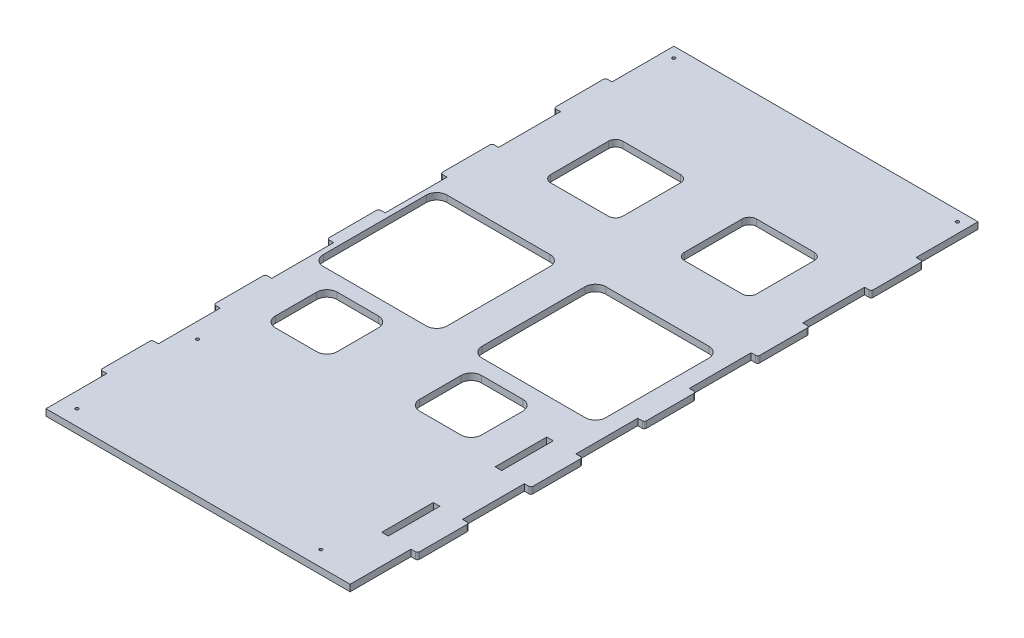
SolidWorks part; units mm, degrees
material "Beech"
ref_plane "Front Plane" through (0, 0, 0) normal (0, 0, 1) x (1, 0, 0)
ref_plane "Top Plane" through (0, 0, 0) normal (0, 1, 0) x (1, 0, 0)
ref_plane "Right Plane" through (0, 0, 0) normal (1, 0, 0) x (0, 0, -1)
sketch "Sketch1" plane through (0, 0, 0) normal (0, 1, 0) x (1, 0, 0)
  line L1 (0, 0) -> (295, 0)
  line L2 (0, 0) -> (0, 59)
  line L3 (0, 609) -> (295, 609)
  line L4 (295, 0) -> (295, 59)
  line L5 (0, 59) -> (-6.35, 59)
  line L7 (0, 109) -> (-6.35, 109)
  line L8 (-6.35, 59) -> (-6.35, 109)
  line L9 (0, 169) -> (-6.35, 169)
  line L10 (-6.35, 169) -> (-6.35, 219)
  line L11 (0, 219) -> (-6.35, 219)
  line L13 (0, 279) -> (-6.35, 279)
  line L14 (-6.35, 279) -> (-6.35, 329)
  line L15 (0, 329) -> (-6.35, 329)
  line L17 (0, 389) -> (-6.35, 389)
  line L18 (-6.35, 389) -> (-6.35, 439)
  line L19 (0, 439) -> (-6.35, 439)
  line L21 (0, 499) -> (-6.35, 499)
  line L22 (-6.35, 499) -> (-6.35, 549)
  line L23 (0, 549) -> (-6.35, 549)
  line L25 (295, 59) -> (301.35, 59)
  line L27 (295, 109) -> (301.35, 109)
  line L28 (301.35, 59) -> (301.35, 109)
  line L29 (295, 169) -> (301.35, 169)
  line L30 (301.35, 169) -> (301.35, 219)
  line L31 (295, 219) -> (301.35, 219)
  line L33 (295, 279) -> (301.35, 279)
  line L34 (301.35, 279) -> (301.35, 329)
  line L35 (295, 329) -> (301.35, 329)
  line L37 (295, 389) -> (301.35, 389)
  line L38 (301.35, 389) -> (301.35, 439)
  line L39 (295, 439) -> (301.35, 439)
  line L41 (295, 499) -> (301.35, 499)
  line L42 (301.35, 499) -> (301.35, 549)
  line L43 (295, 549) -> (301.35, 549)
  line L44 (0, 549) -> (0, 609)
  line L46 (0, 329) -> (0, 389)
  line L49 (0, 219) -> (0, 279)
  line L50 (0, 109) -> (0, 169)
  line L51 (295, 109) -> (295, 169)
  line L52 (295, 219) -> (295, 279)
  line L53 (295, 329) -> (295, 389)
  line L54 (295, 439) -> (295, 499)
  line L55 (295, 549) -> (295, 609)
  line L56 (0, 439) -> (0, 499)
  dimension "D1" = 609
  dimension "D2" = 295
  dimension "D3" = 6.35
  dimension "D4" = 50
  dimension "D5" = 59
  dimension "D7" = 60
  dimension "D8" = 50
  dimension "D9" = 6.35
  dimension "D11" = 59
  dimension "D12" = 60
  dimension "D6" = 5
  dimension "D10" = 5
extrude "Boss-Extrude1" add sketch "Sketch1" along normal blind 6.35
fillet "Fillet1" radius 2 20 edges at (301.35, 3.175, -549) (301.35, 3.175, -499) (301.35, 3.175, -439) (301.35, 3.175, -389) (301.35, 3.175, -329) (301.35, 3.175, -279) (301.35, 3.175, -219) (301.35, 3.175, -169) (301.35, 3.175, -109) (301.35, 3.175, -59) (-6.35, 3.175, -59) (-6.35, 3.175, -109) (-6.35, 3.175, -169) (-6.35, 3.175, -219) (-6.35, 3.175, -279) (-6.35, 3.175, -329) (-6.35, 3.175, -389) (-6.35, 3.175, -439) (-6.35, 3.175, -499) (-6.35, 3.175, -549)
sketch "Sketch2" plane through (0, 6.35, 0) normal (0, 1, 0) x (1, 0, 0)
  line L0 (266.65, 0) -> (266.65, 100) construction
  line L1 (0, 0) -> (295, 0) construction
  line L2 (0, 609) -> (0, 0) construction
  line L3 (295, 609) -> (295, 0) construction
  line L4 (0, 150) -> (266.65, 100) construction
  line L5 (266.65, 169) -> (266.65, 219)
  line L6 (266.65, 59) -> (273, 59)
  line L7 (266.65, 59) -> (266.65, 109)
  line L8 (266.65, 109) -> (273, 109)
  line L9 (273, 59) -> (273, 109)
  line L10 (266.65, 169) -> (273, 169)
  line L11 (273, 169) -> (273, 219)
  line L12 (266.65, 219) -> (273, 219)
  line L13 (0, 84.2124) -> (266.65, 84) construction
  line L14 (55.0424, 504.4355) -> (111.0424, 504.4355)
  line L15 (48.0424, 497.4355) -> (48.0424, 441.4355)
  line L16 (55.0424, 434.4355) -> (111.0424, 434.4355)
  line L17 (118.0424, 497.4355) -> (118.0424, 441.4355)
  line L18 (185.2335, 503.9695) -> (241.2335, 503.9695)
  line L19 (178.2335, 496.9695) -> (178.2335, 440.9695)
  line L20 (185.2335, 433.9695) -> (241.2335, 433.9695)
  line L21 (248.2335, 496.9695) -> (248.2335, 440.9695)
  line L22 (43.325, 239.1432) -> (83.325, 239.1432)
  line L23 (33.325, 229.1432) -> (33.325, 189.1432)
  line L24 (43.325, 179.1432) -> (83.325, 179.1432)
  line L25 (93.325, 229.1432) -> (93.325, 189.1432)
  line L26 (33.325, 239.1432) -> (93.325, 179.1432) construction
  line L27 (33.325, 179.1432) -> (93.325, 239.1432) construction
  line L32 (133.325, 0) -> (133.325, 609) construction
  line L33 (295, 609) -> (0, 609) construction
  line L34 (5, 373.9596) -> (125, 373.9596)
  line L35 (5, 373.9596) -> (5, 253.9596)
  line L36 (5, 253.9596) -> (125, 253.9596)
  line L37 (125, 373.9596) -> (125, 253.9596)
  line L38 (159, 373.9596) -> (279, 373.9596)
  line L39 (159, 373.9596) -> (159, 253.9596)
  line L40 (159, 253.9596) -> (279, 253.9596)
  line L41 (279, 373.9596) -> (279, 253.9596)
  line L42 (233.325, 179.1432) -> (173.325, 239.1432) construction
  line L43 (233.325, 239.1432) -> (173.325, 179.1432) construction
  line L44 (173.325, 229.1432) -> (173.325, 189.1432)
  line L45 (223.325, 179.1432) -> (183.325, 179.1432)
  line L46 (233.325, 229.1432) -> (233.325, 189.1432)
  line L47 (223.325, 239.1432) -> (183.325, 239.1432)
  arc A0 (48.0424, 441.4355) -> (55.0424, 434.4355) centre (55.0424, 441.4355) ccw
  arc A1 (111.0424, 434.4355) -> (118.0424, 441.4355) centre (111.0424, 441.4355) ccw
  arc A2 (111.0424, 504.4355) -> (118.0424, 497.4355) centre (111.0424, 497.4355) cw
  arc A3 (55.0424, 504.4355) -> (48.0424, 497.4355) centre (55.0424, 497.4355) ccw
  arc A4 (178.2335, 440.9695) -> (185.2335, 433.9695) centre (185.2335, 440.9695) ccw
  arc A5 (241.2335, 433.9695) -> (248.2335, 440.9695) centre (241.2335, 440.9695) ccw
  arc A6 (241.2335, 503.9695) -> (248.2335, 496.9695) centre (241.2335, 496.9695) cw
  arc A7 (185.2335, 503.9695) -> (178.2335, 496.9695) centre (185.2335, 496.9695) ccw
  arc A8 (33.325, 189.1432) -> (43.325, 179.1432) centre (43.325, 189.1432) ccw
  arc A9 (83.325, 179.1432) -> (93.325, 189.1432) centre (83.325, 189.1432) ccw
  arc A10 (83.325, 239.1432) -> (93.325, 229.1432) centre (83.325, 229.1432) cw
  arc A11 (43.325, 239.1432) -> (33.325, 229.1432) centre (43.325, 229.1432) ccw
  arc A16 (223.325, 239.1432) -> (233.325, 229.1432) centre (223.325, 229.1432) cw
  arc A17 (183.325, 239.1432) -> (173.325, 229.1432) centre (183.325, 229.1432) ccw
  arc A18 (183.325, 179.1432) -> (173.325, 189.1432) centre (183.325, 189.1432) cw
  arc A19 (233.325, 189.1432) -> (223.325, 179.1432) centre (223.325, 189.1432) cw
  circle A20 centre (15, 15) radius 1.5
  circle A21 centre (251.65, 15) radius 1.5
  circle A22 centre (15, 131.9259) radius 1.5
  circle A23 centre (10, 599) radius 1.5
  circle A24 centre (285, 599) radius 1.5
  point P33 (118.0424, 434.4355)
  point P36 (118.0424, 504.4355)
  point P39 (48.0424, 504.4355)
  point P42 (178.2335, 433.9695)
  point P47 (248.2335, 503.9695)
  point P50 (178.2335, 503.9695)
  point P51 (63.325, 209.1432)
  point P74 (133.325, 84.1062)
  point P99 (203.325, 209.1432)
  dimension "D10" = 7
  dimension "D11" = 7
  dimension "D16" = 10
  dimension "D17" = 70
  dimension "D22" = 3
  dimension "D25" = 3
  dimension "D28" = 3
  dimension "D18" = 3
  dimension "D31" = 3
  dimension "D1" = 100
  dimension "D2" = 150
  dimension "D3" = 6.35
  dimension "D4" = 50
  dimension "D6" = 70
  dimension "D7" = 70
  dimension "D8" = 70
  dimension "D9" = 70
  dimension "D12" = 60
  dimension "D13" = 60
  dimension "D14" = 22
  dimension "D15" = 59
  dimension "12" = 120
  dimension "D19" = 120
  dimension "D20" = 120
  dimension "D21" = 120
  dimension "D23" = 15
  dimension "D24" = 15
  dimension "D26" = 15
  dimension "D27" = 15
  dimension "D29" = 15
  dimension "D30" = 15
  dimension "D32" = 10
  dimension "D33" = 10
  dimension "D34" = 10
  dimension "D35" = 10
  dimension "D36" = 5
  dimension "D37" = 16
  dimension "D5" = 2
extrude "Cut-Extrude1" cut sketch "Sketch2" against normal blind 6.35
fillet "Fillet2" radius 10 8 edges at (125, 3.175, -253.9596) (5, 3.175, -253.9596) (5, 3.175, -373.9596) (125, 3.175, -373.9596) (159, 3.175, -253.9596) (279, 3.175, -253.9596) (279, 3.175, -373.9596) (159, 3.175, -373.9596)
